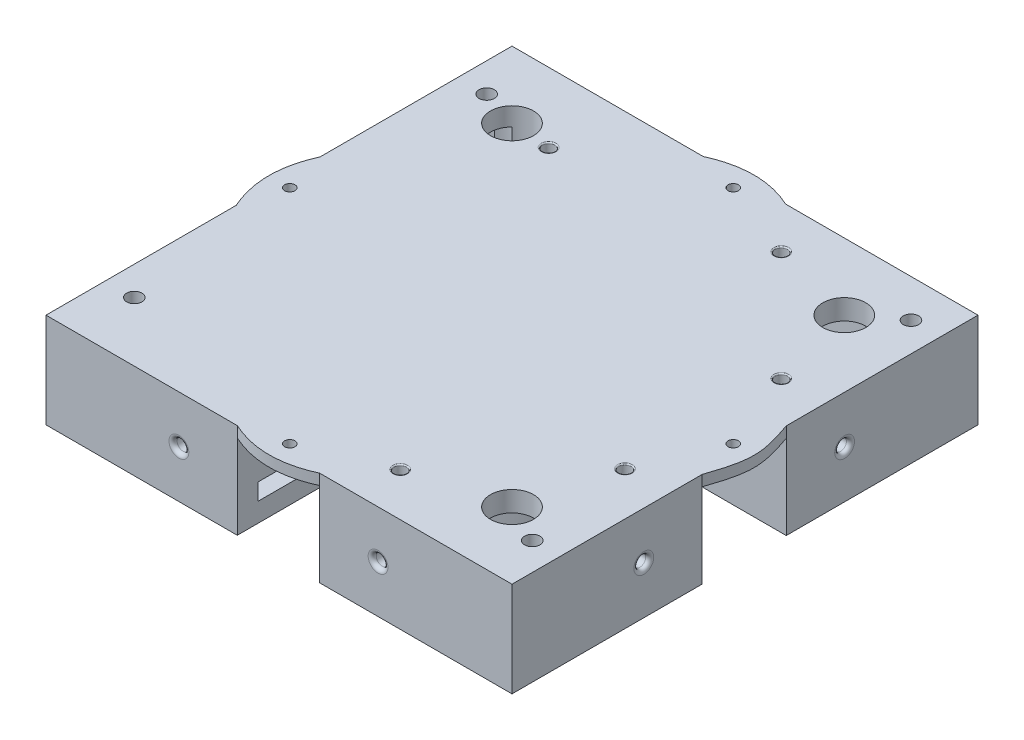
SolidWorks part; units mm, degrees
material "5052-H32"
ref_plane "Front Plane" through (0, 0, 0) normal (0, 0, 1) x (1, 0, 0)
ref_plane "Top Plane" through (0, 0, 0) normal (0, 1, 0) x (1, 0, 0)
ref_plane "Right Plane" through (0, 0, 0) normal (1, 0, 0) x (0, 0, -1)
sketch "Sketch1" plane through (6.2102, 0, 5.115) normal (0, 1, 0) x (1, 0, 0)
  line L1 (-55.0729, 54.0753) -> (42.5271, 54.0753)
  line L2 (-55.0729, 54.0753) -> (-55.0729, -43.5247)
  line L3 (-55.0729, -43.5247) -> (42.5271, -43.5247)
  line L4 (42.5271, 54.0753) -> (42.5271, -43.5247)
  dimension "D1" = 97.6
  dimension "D2" = 97.6
extrude "Boss-Extrude1" add sketch "Sketch1" along normal blind 19.9
sketch "Sketch2" plane through (6.2102, 19.9, 5.115) normal (0, 1, 0) x (1, 0, 0)
  line L0 (42.5271, -43.5247) -> (42.5271, 54.0753) construction
  line L1 (-55.0729, -43.5247) -> (42.5271, -43.5247) construction
  circle A0 centre (28.5271, -29.5247) radius 4.5
  dimension "D1" = 9
  dimension "D2" = 14
  dimension "D3" = 14
sketch "Sketch3" plane through (6.2102, 19.9, 5.115) normal (0, 1, 0) x (1, 0, 0)
  line L0 (42.5271, -43.5247) -> (42.5271, 54.0753) construction
  line L1 (42.5271, 54.0753) -> (-55.0729, 54.0753) construction
  line L2 (-55.0729, 54.0753) -> (-55.0729, -43.5247) construction
  circle A0 centre (28.5271, 40.0753) radius 4.5
  circle A1 centre (-41.0729, 40.0753) radius 4.5
  dimension "D1" = 9
  dimension "D2" = 14
  dimension "D3" = 14
  dimension "D4" = 9
  dimension "D5" = 14
  dimension "D6" = 14
sketch "Sketch5" plane through (6.2102, 19.9, 5.115) normal (0, 1, 0) x (1, 0, 0)
  line L1 (-55.0729, 54.0753) -> (-55.0729, -43.5247) construction
  line L3 (-55.0729, -43.5247) -> (42.5271, -43.5247) construction
  circle A0 centre (-6.2729, 5.2753) radius 50.775
  dimension "D1" = 48.8
  dimension "D2" = 48.8
extrude "Cut-Extrude3" cut sketch "Sketch2" against normal blind 19.9 contours A0
extrude "Cut-Extrude5" cut sketch "Sketch3" against normal blind 19.9
sketch "Sketch7" plane through (6.2102, 19.9, 5.115) normal (0, 1, 0) x (1, 0, 0)
  line L0 (42.5271, -43.5247) -> (42.5271, 54.0753) construction
  line L1 (42.5271, 54.0753) -> (-55.0729, 54.0753) construction
  line L2 (42.5271, -43.5247) -> (42.5271, 54.0753) construction
  line L3 (-55.0729, -43.5247) -> (42.5271, -43.5247) construction
  line L4 (42.5271, 54.0753) -> (-55.0729, 54.0753) construction
  line L5 (-55.0729, 54.0753) -> (-55.0729, -43.5247) construction
  line L6 (-55.0729, 54.0753) -> (-55.0729, -43.5247) construction
  line L7 (-55.0729, -43.5247) -> (42.5271, -43.5247) construction
  circle A0 centre (36.4271, 46.1353) radius 1.6
  circle A1 centre (36.7271, -33.4747) radius 1.6
  circle A2 centre (-49.0229, 42.7253) radius 1.6
  circle A3 centre (-49.0229, -31.0747) radius 1.6
  dimension "D1" = 6.1
  dimension "D2" = 7.94
  dimension "D3" = 5.8
  dimension "D4" = 10.05
  dimension "D5" = 11.35
  dimension "D6" = 6.05
  dimension "D7" = 6.05
  dimension "D8" = 12.45
extrude "Cut-Extrude6" cut sketch "Sketch7" against normal blind 19.9
sketch "Sketch9" plane through (6.2102, 19.9, 5.115) normal (0, 1, 0) x (1, 0, 0)
  line L0 (42.5271, -43.5247) -> (42.5271, 54.0753) construction
  line L1 (42.5271, 54.0753) -> (-55.0729, 54.0753) construction
  line L2 (42.5271, -43.5247) -> (42.5271, 54.0753) construction
  line L3 (-55.0729, -43.5247) -> (42.5271, -43.5247) construction
  line L4 (42.5271, 54.0753) -> (-55.0729, 54.0753) construction
  line L5 (-55.0729, 54.0753) -> (-55.0729, -43.5247) construction
  circle A0 centre (33.4271, 21.9753) radius 1.3
  circle A1 centre (33.4271, -10.7747) radius 1.3
  circle A2 centre (10.4271, 44.9753) radius 1.3
  circle A3 centre (10.0271, -34.4247) radius 1.3
  circle A4 centre (-32.8529, 39.5253) radius 1.3
  dimension "D1" = 9.1
  dimension "D2" = 32.1
  dimension "D3" = 9.1
  dimension "D5" = 9.1
  dimension "D7" = 32.5
  dimension "D9" = 14.55
  dimension "D4" = 32.75
  dimension "D6" = 32.1
  dimension "D8" = 9.1
  dimension "D10" = 22.22
extrude "Cut-Extrude12" cut sketch "Sketch9" against normal blind 19.9
fillet "Fillet2" radius 0.25 1 edges at (16.6373, 19.9, -38.5603)
fillet "Fillet3" radius 0.25 1 edges at (39.6373, 19.9, -15.5603)
fillet "Fillet5" radius 0.25 3 edges at (16.2373, 19.9, 40.8397) (39.6373, 19.9, 17.1897) (-26.6427, 19.9, -33.1103)
sketch "Sketch16" plane through (0, 19.9, 0) normal (0, 1, 0) x (1, 0, 0)
  line L0 (-48.8627, 8.8) -> (-48.8627, -8.8)
  line L1 (-48.8627, 48.9603) -> (-48.8627, -48.6397) construction
  line L2 (0, 35.791) -> (0, -31.7052) construction
  line L3 (-25.3041, 0.1603) -> (24.6208, 0.1603) construction
  line L4 (48.7373, -48.6397) -> (48.7373, 48.9603) construction
  line L5 (-8.8, 48.9603) -> (8.8, 48.8)
  line L6 (48.7373, 48.9603) -> (-48.8627, 48.9603) construction
  line L7 (-8.8, -48.6397) -> (8.8, -48.4794)
  line L8 (48.7373, 8.8) -> (48.7373, -8.8)
  circle A0 centre (-0.0627, 0.1603) radius 50.775 construction
  spline S0 degree 2 poles (-48.8627, -8.8) (-52.8139, 0.0154) (-48.8627, 8.8) knots 0 0 0 1 1 1
  spline S1 degree 3 poles (48.7373, 8.8) (49.7135, 5.9213) (51.7006, 0.0624) (49.7364, -5.8119) (48.7373, -8.8) knots 0 0 0 0 0.491329 1 1 1 1
  spline S2 degree 2 poles (-8.8, 48.9603) (0.029, 52.9893) (8.8, 48.8) knots 0 0 0 1 1 1
  spline S3 degree 2 poles (-8.8, -48.6397) (0.029, -52.6688) (8.8, -48.4794) knots 0 0 0 1 1 1
  point P4 (-50.8375, 0)
  point P14 (48.7373, 8.8)
  point P15 (48.7373, -8.8)
  point P17 (50.712, 0)
  point P22 (0, 50.9353)
  point P27 (0, -50.6147)
extrude "Boss-Extrude3" add sketch "Sketch16" against normal blind 2.25
sketch "Sketch17" plane through (0, 19.9, 0) normal (0, 1, 0) x (1, 0, 0)
  line L0 (0, 36.9512) -> (0, -38.1962) construction
  line L1 (-17.9287, 0) -> (21.0682, 0) construction
  circle A0 centre (46.44, 0) radius 1.085
  circle A1 centre (-46.44, 0) radius 1.085
  circle A2 centre (0, 46.44) radius 1.085
  circle A3 centre (0, -46.44) radius 1.085
extrude "Cut-Extrude13" cut sketch "Sketch17" against normal blind 19.9
sketch "Sketch18" plane through (0, 0, 0) normal (0, -1, 0) x (1, 0, 0)
  line L0 (48.7373, 48.6397) -> (48.7373, -48.9603) construction
  line L1 (-48.8627, -8.8) -> (48.7373, -8.8)
  line L2 (-48.8627, -8.8) -> (-48.8627, 8.8)
  line L3 (-48.8627, 8.8) -> (48.7373, 8.8)
  line L4 (48.7373, -8.8) -> (48.7373, 8.8)
  line L5 (48.7373, -8.8) -> (48.7373, 8.8) construction
  line L7 (-8.8, 48.6397) -> (8.4578, 48.6397)
  line L8 (-8.8, 48.6397) -> (-8.8, -48.9603)
  line L9 (-8.8, -48.9603) -> (8.4578, -48.9603)
  line L10 (8.4578, 48.6397) -> (8.4578, -48.9603)
  circle A0 centre (0, 0) radius 32.5
extrude "Cut-Extrude14" cut sketch "Sketch18" against normal blind 17.65 contours L1 L4 L3 L2
sketch "Sketch19" plane through (0, 0, 0) normal (0, -1, 0) x (1, 0, 0)
  line L1 (-8.8, 48.6397) -> (8.4578, 48.6397)
  line L2 (-8.8, 48.6397) -> (-8.8, -48.9603)
  line L3 (-8.8, -48.9603) -> (8.4578, -48.9603)
  line L4 (8.4578, 48.6397) -> (8.4578, -48.9603)
extrude "Cut-Extrude15" cut sketch "Sketch19" against normal blind 17.65
sketch "Sketch20" plane through (0, 0, 0) normal (0, -1, 0) x (1, 0, 0)
  circle A0 centre (0, 0) radius 32.5
extrude "Cut-Extrude16" cut sketch "Sketch20" against normal blind 17.65
sketch "Sketch21" plane through (0, 0, 0) normal (0, -1, 0) x (-1, 0, 0)
  line L0 (-14.6078, 44.6603) -> (-36.2373, 44.6603)
  line L1 (-42.5873, 37.4103) -> (-52.6816, 37.4103) construction
  line L2 (-38.5119, 37.4103) -> (-42.5873, 37.4103)
  line L3 (-44.4373, 14.95) -> (-44.4373, 35.5603)
  line L4 (-38.0873, 42.8103) -> (-38.0873, 37.9649)
  line L8 (-31.2859, 8.8) -> (-48.7373, 8.8) construction
  line L9 (-31.2859, 8.8) -> (-48.7373, 8.8) construction
  line L10 (-44.4373, 14.95) -> (-40.3393, 14.95) construction
  line L11 (-42.5859, 13.1) -> (-33.9942, 13.1062)
  line L13 (-12.7578, 34.1264) -> (-12.7578, 42.8103)
  arc A1 (-36.2373, 44.6603) -> (-38.0873, 42.8103) centre (-36.2373, 42.8103) ccw
  circle A2 centre (-34.7373, 34.9603) radius 4.5 construction
  arc A3 (-44.4373, 14.95) -> (-42.5859, 13.1) centre (-42.5873, 14.95) ccw
  arc A4 (-33.9942, 13.1062) -> (-12.7578, 34.1264) centre (0, 0) cw
  arc A5 (-14.6078, 44.6603) -> (-12.7578, 42.8103) centre (-14.6078, 42.8103) cw
  arc A6 (-38.0873, 37.9649) -> (-38.5119, 37.4103) centre (-34.7373, 34.9603) ccw
  arc A7 (-42.5873, 37.4103) -> (-44.4373, 35.5603) centre (-42.5873, 35.5603) ccw
  point P4 (-12.7578, 42.8103)
  point P9 (-38.0914, 42.8103)
  point P16 (-44.4373, 35.5603)
  point P24 (-42.5873, 13.1)
  dimension "D1" = 1.85
  dimension "D7" = 6.15
  dimension "D9" = 4.3
sketch "Sketch24" plane through (0, 0, 0) normal (0, -1, 0) x (-1, 0, 0)
  line L0 (-12.7636, -42.5054) -> (-12.7636, -34.5156)
  line L2 (-30.2373, -34.6397) -> (-39.2373, -34.6397) construction
  line L3 (-48.7373, -48.6397) -> (-48.7373, -8.8) construction
  line L4 (-44.4373, -14.95) -> (-44.4373, -34.5)
  line L5 (-42.5873, -36.35) -> (-38.8996, -36.35)
  line L6 (-37.9519, -37.7887) -> (-37.9519, -42.4897)
  line L8 (-36.1019, -44.3397) -> (-14.6078, -44.3397)
  line L10 (-34.3894, -13.1) -> (-42.5873, -13.1)
  arc A0 (-42.5873, -13.1) -> (-44.4373, -14.95) centre (-42.5873, -14.95) ccw
  arc A1 (-44.4373, -34.5) -> (-42.5873, -36.35) centre (-42.5873, -34.5) ccw
  circle A2 centre (-34.7373, -34.6397) radius 4.5 construction
  arc A3 (-38.8996, -36.35) -> (-37.9519, -37.7887) centre (-34.7373, -34.6397) ccw
  arc A4 (-37.9519, -42.4897) -> (-36.1019, -44.3397) centre (-36.1019, -42.4897) ccw
  arc A5 (-14.6078, -44.3397) -> (-12.7636, -42.5054) centre (-14.6136, -42.4897) ccw
  arc A6 (-12.7636, -34.5156) -> (-34.3894, -13.1) centre (0, 0) cw
  point P7 (-44.4373, -14.95)
  point P11 (-42.5873, -36.35)
  point P23 (-36.1019, -44.3397)
  point P27 (-12.7578, -42.4897)
  dimension "D2" = 6.15
extrude "Cut-Extrude19" cut sketch "Sketch24" against normal blind 13
sketch "Sketch25" plane through (0, 13, 0) normal (0, -1, 0) x (1, 0, 0)
  line L0 (42.5873, 18.6797) -> (34.1918, 18.6797)
  line L1 (44.4373, 14.95) -> (44.4373, 34.5) construction
  line L2 (44.4373, 20.5297) -> (44.4373, 34.5)
  line L3 (44.4373, 14.95) -> (44.4373, 34.5) construction
  line L4 (42.5873, 36.35) -> (38.8996, 36.35)
  line L5 (42.5873, 36.35) -> (38.8996, 36.35) construction
  line L6 (36.1019, 44.3397) -> (14.6078, 44.3397) construction
  line L7 (19.7073, 42.4897) -> (19.7073, 34.6397)
  line L8 (33.5229, 38.9727) -> (33.5229, 42.4897)
  line L9 (36.1019, 44.3397) -> (14.6078, 44.3397) construction
  line L10 (21.5573, 44.3397) -> (31.6729, 44.3397)
  arc A0 (42.5873, 18.6797) -> (44.4373, 20.5297) centre (42.5873, 20.5297) ccw
  arc A1 (44.4373, 34.5) -> (42.5873, 36.35) centre (42.5873, 34.5) ccw
  arc A2 (44.4373, 34.5) -> (42.5873, 36.35) centre (42.5873, 34.5) ccw construction
  arc A3 (19.7073, 42.4897) -> (21.5573, 44.3397) centre (21.5573, 42.4897) cw
  arc A4 (38.8996, 36.35) -> (33.5229, 38.9727) centre (34.7373, 34.6397) ccw
  arc A5 (33.5229, 42.4897) -> (31.6729, 44.3397) centre (31.6729, 42.4897) ccw
  arc A7 (34.3894, 13.1) -> (12.7636, 34.5156) centre (0, 0) ccw construction
  arc A8 (20.5983, 30.4951) -> (30.5272, 20.5506) centre (0, 0) cw
  spline S0 degree 2 poles (34.1918, 18.6797) (31.9769, 18.8503) (30.5272, 20.5506) knots 0 0 0 1 1 1
  spline S1 degree 2 poles (19.7073, 34.6397) (19.7281, 32.4756) (20.5983, 30.4951) knots 0 0 0 1 1 1
  point P2 (44.4373, 20.5297)
  point P21 (31.6729, 44.3397)
  point P28 (21.5573, 44.3397)
  point P34 (32.2408, 19.1964)
  point P39 (20.5983, 30.4951)
  point P41 (19.9449, 32.5008)
extrude "Cut-Extrude20" cut sketch "Sketch25" against normal blind 2.65
extrude "Cut-Extrude21" cut sketch "Sketch21" against normal blind 13
sketch "Sketch27" plane through (0, 0, 0) normal (0, -1, 0) x (1, 0, 0)
  line L0 (-35.6365, 44.3397) -> (-14.9738, 44.3397)
  line L1 (-13.1, 42.4899) -> (-13.1, 34.3894)
  line L2 (-34.3894, 13.1) -> (-42.7127, 13.1)
  line L3 (-48.8627, 8.8) -> (-48.8627, 48.6397) construction
  line L4 (-37.4865, 42.4897) -> (-37.4865, 38.6397)
  line L5 (-50.8377, -0.1603) -> (50.7123, -0.1603) construction
  line L6 (-0.0627, 50.6147) -> (-0.0627, -50.9353) construction
  line L8 (-44.5627, 35.5497) -> (-44.5627, 14.95)
  line L9 (-37.4865, 38.6397) -> (-42.7127, 38.6397)
  arc A0 (-14.9738, 44.3397) -> (-13.1, 42.4899) centre (-14.95, 42.4899) cw
  circle A1 centre (-0.0627, -0.1603) radius 50.775 construction
  arc A2 (-13.1, 34.3894) -> (-34.3894, 13.1) centre (0, 0) ccw
  arc A3 (-35.6365, 44.3397) -> (-37.4865, 42.4897) centre (-35.6365, 42.4897) ccw
  arc A4 (-42.7127, 13.1) -> (-44.5627, 14.95) centre (-42.7127, 14.95) cw
  circle A5 centre (-42.8127, 36.1897) radius 1.6 construction
  arc A6 (-42.7127, 38.6397) -> (-44.4062, 36.0449) centre (-42.7127, 36.7897) ccw
  arc A7 (-44.4062, 36.0449) -> (-44.5627, 35.5497) centre (-43.2956, 35.4214) ccw
  parabola Q0 (-8.8, 48.6397) -> (8.4578, 48.6397) focus (-0.0906, 41.1914) apex (-0.0241, 50.6145) construction
  point P2 (-37.4627, 42.4897)
  point P21 (-13.1, 42.4897)
  point P24 (-42.7127, 13.1)
  point P31 (-44.5627, 14.95)
  dimension "D2" = 6.15
extrude "Cut-Extrude22" cut sketch "Sketch27" against normal blind 15.65
sketch "Sketch28" plane through (0, 0, 0) normal (0, -1, 0) x (1, 0, 0)
  line L0 (-42.7127, -13.1) -> (-34.3894, -13.1)
  line L1 (-44.4037, -37.4409) -> (-44.4037, -14.95)
  line L2 (-38.0447, -38.1423) -> (-38.0447, -42.8103)
  line L3 (-36.1947, -44.6603) -> (-14.95, -44.6603)
  line L4 (-8.8, -31.2859) -> (-8.8, -48.9603) construction
  line L5 (-13.1, -34.3894) -> (-13.1, -42.8103)
  line L10 (-8.8, -48.9603) -> (-48.8627, -48.9603) construction
  arc A0 (-42.7127, -13.1) -> (-44.4037, -14.95) centre (-42.5463, -14.95) ccw
  circle A1 centre (-42.8127, -37.6103) radius 1.6 construction
  circle A2 centre (-34.8627, -34.9603) radius 4.5 construction
  circle A3 centre (-42.8127, -37.6103) radius 1.6
  arc A4 (-38.0447, -42.8103) -> (-36.1947, -44.6603) centre (-36.1947, -42.8103) ccw
  arc A5 (-14.95, -44.6603) -> (-13.1, -42.8103) centre (-14.95, -42.8103) ccw
  arc A6 (-13.1, -34.3894) -> (-34.3894, -13.1) centre (0, 0) cw
  spline S0 degree 2 poles (-38.0447, -38.1423) (-39.7881, -41.8175) (-42.8127, -39.2103) knots 0 0 0 1 1 1
  point P4 (-44.5627, -14.95)
  point P14 (-36.1947, -44.6603)
  point P24 (-40.1783, -40.2611)
  point P27 (-13.1, -42.8103)
  circle M12 centre (-34.8627, -34.9603) radius 4.5
  circle M13 centre (-42.8127, -37.6103) radius 1.6
  circle M14 centre (-26.6427, -34.4103) radius 1.3
  dimension "D1" = 10.818
  dimension "D2" = 6.15
extrude "Cut-Extrude23" cut sketch "Sketch28" against normal blind 9.2 contours S0 L2 A4 L3 A5 L5 A6 L0 A0 L1 M12 M13 M14 | A3 M13 | M12 region at (-34.8627, 0, -34.9603) region at (-30.9777, 0, -31.133) region at (-42.8127, 0, -37.6103)
sketch "Sketch30" plane through (0, 9.2, 0) normal (0, -1, 0) x (1, 0, 0)
  line L0 (-34.3894, -13.1) -> (-42.7127, -13.1)
  line L1 (-44.4037, -14.95) -> (-44.4037, -37.4409)
  line L2 (-39.3627, -34.9603) -> (-30.3627, -34.9603) construction
  line L3 (-27.6026, -27.7002) -> (-31.6807, -31.7783)
  arc A1 (-34.3894, -13.1) -> (-13.1, -34.3894) centre (0, 0) ccw construction
  arc A2 (-26.9237, -25.087) -> (-34.3894, -13.1) centre (0, 0) cw
  arc A3 (-42.7127, -13.1) -> (-44.4037, -14.95) centre (-42.5463, -14.95) ccw
  circle A5 centre (-34.8627, -34.9603) radius 4.5 construction
  arc A7 (-42.8127, -39.2103) -> (-44.4037, -37.4409) centre (-42.8127, -37.6103) ccw construction
  arc A8 (-38.0447, -38.1423) -> (-31.6807, -31.7783) centre (-34.8627, -34.9603) cw
  arc A9 (-42.8127, -39.2103) -> (-44.4037, -37.4409) centre (-42.8127, -37.6103) ccw
  parabola Q2 (-38.0447, -38.1423) -> (-42.8127, -39.2103) focus (-40.3293, -39.3425) apex (-40.1433, -40.2543) construction
  parabola Q3 (-38.0447, -38.1423) -> (-42.8127, -39.2103) focus (-40.3293, -39.3425) apex (-40.1433, -40.2543)
  spline S0 degree 2 poles (-27.6026, -27.7002) (-26.4881, -26.626) (-26.9237, -25.087) knots 0 0 0 1 1 1
  point P4 (-44.4037, -14.95)
  point P9 (-26.9237, -26.67)
  point P10 (-26.9237, -25.087)
  point P24 (-40.199, -40.2684)
  point P27 (-38.0447, -38.1423)
extrude "Cut-Extrude24" cut sketch "Sketch30" against normal blind 6.85 contours L3 S0 A2 L0 A3 L1 A9 Q3 A8 region at (-37.6678, 9.2, -24.4447)
sketch "Sketch31" plane through (0, 13, 0) normal (0, -1, 0) x (1, 0, 0)
  line L0 (38.5119, -37.4103) -> (42.5873, -37.4103)
  line L1 (38.5119, -37.4103) -> (42.5873, -37.4103) construction
  line L2 (31.4637, -20.613) -> (42.5873, -20.613)
  line L3 (44.4373, -35.5603) -> (44.4373, -22.463)
  line L4 (22.3673, -44.6603) -> (32.8873, -44.6603)
  line L6 (34.7373, -39.4603) -> (34.7373, -42.8103)
  line L8 (20.5173, -42.8103) -> (20.5173, -31.9104)
  arc A0 (38.5119, -37.4103) -> (38.0873, -37.9649) centre (34.7373, -34.9603) ccw construction
  arc A1 (34.7373, -39.4603) -> (38.5119, -37.4103) centre (34.7373, -34.9603) cw
  arc A2 (42.5873, -37.4103) -> (44.4373, -35.5603) centre (42.5873, -35.5603) ccw
  arc A3 (42.5873, -37.4103) -> (44.4373, -35.5603) centre (42.5873, -35.5603) ccw construction
  arc A4 (34.7373, -42.8103) -> (32.8873, -44.6603) centre (32.8873, -42.8103) cw
  arc A5 (22.3673, -44.6603) -> (20.5173, -42.8103) centre (22.3673, -42.8103) cw
  arc A6 (44.4373, -22.463) -> (42.5873, -20.613) centre (42.5873, -22.463) ccw
  arc A7 (12.7578, -34.1264) -> (33.9942, -13.1062) centre (0, 0) ccw construction
  arc A8 (21.7165, -29.2536) -> (29.4236, -21.4855) centre (0, 0) ccw
  spline S0 degree 2 poles (31.4637, -20.613) (30.2943, -20.696) (29.4236, -21.4855) knots 0 0 0 1 1 1
  spline S1 degree 2 poles (20.5173, -31.9104) (20.595, -30.3481) (21.7165, -29.2536) knots 0 0 0 1 1 1
  point P0 (44.4373, -35.5603)
  point P13 (22.3673, -44.6603)
  point P19 (44.4373, -22.463)
  point P20 (30.3942, -20.862)
  point P22 (29.4236, -21.4855)
  point P26 (21.7165, -29.2536)
  point P34 (32.8873, -44.6603)
  point P37 (20.8481, -30.4826)
extrude "Cut-Extrude26" cut sketch "Sketch31" against normal blind 2.65
sketch "Sketch32" plane through (0, 0, 48.6397) normal (0, 0, 1) x (1, 0, 0)
  circle A0 centre (-21.025, 9.95) radius 1.225
  circle A1 centre (20.6828, 9.95) radius 1.225
extrude "Cut-Extrude27" cut sketch "Sketch32" against normal blind 4.4
fillet "Fillet6" radius 0.85 1 edges at (-19.8, 9.95, 48.6397)
fillet "Fillet7" radius 0.85 1 edges at (19.4578, 9.95, 48.6397)
sketch "Sketch33" plane through (48.7373, 0, 0) normal (1, 0, 0) x (0, 0, -1)
  line L0 (50.9353, 19.9) -> (-50.6147, 19.9) construction
  line L1 (-8.8, 17.65) -> (-8.8, 0) construction
  line L3 (-8.8, 17.65) -> (8.8, 17.65) construction
  line L4 (0, 17.65) -> (0, -3.9996) construction
  line L5 (8.8, 17.65) -> (8.8, 0) construction
  line L6 (8.8, 0) -> (48.9603, 0) construction
  line L7 (8.8, 19.9) -> (48.9603, 19.9) construction
  circle A0 centre (-21.025, 9.95) radius 1.225
  circle A1 centre (21.025, 9.95) radius 1.225
  dimension "D1" = 9.95
  dimension "D2" = 12.225
  dimension "D5" = 2.45
  dimension "D6" = 9.95
  dimension "D7" = 9.95
  dimension "D8" = 21.025
  dimension "D9" = 21.025
  dimension "D3" = 8.8
  dimension "D4" = 8.8
extrude "Cut-Extrude28" cut sketch "Sketch33" against normal blind 4.4
fillet "Fillet8" radius 0.85 1 edges at (48.7373, 9.95, 19.8)
fillet "Fillet9" radius 0.85 1 edges at (48.7373, 9.95, -19.8)
sketch "Sketch34" plane through (0, 0, -48.9603) normal (0, 0, -1) x (-1, 0, 0)
  line L0 (50.8377, 19.9) -> (-50.7123, 19.9) construction
  line L2 (-8.4578, 17.65) -> (-8.4578, 0) construction
  line L3 (-8.4578, 17.65) -> (8.8, 17.65) construction
  line L4 (0.1711, 17.65) -> (0.1711, -9.8959) construction
  line L5 (8.8, 17.65) -> (8.8, 0) construction
  circle A0 centre (-20.6828, 9.95) radius 1.225
  circle A1 centre (21.025, 9.95) radius 1.225
  dimension "D1" = 9.95
  dimension "D2" = 12.225
  dimension "D3" = 12.225
extrude "Cut-Extrude29" cut sketch "Sketch34" against normal blind 6.5
fillet "Fillet10" radius 0.85 1 edges at (19.4578, 9.95, -48.9603)
fillet "Fillet11" radius 0.85 1 edges at (-19.8, 9.95, -48.9603)
sketch "Sketch35" plane through (-48.8627, 0, 0) normal (-1, 0, 0) x (0, 0, 1)
  line L0 (50.6147, 19.9) -> (-50.9353, 19.9) construction
  circle A0 centre (-21.025, 9.95) radius 1.225
  circle A1 centre (21.025, 9.95) radius 1.225
  dimension "D1" = 9.95
extrude "Cut-Extrude30" cut sketch "Sketch35" against normal blind 4.4
fillet "Fillet12" radius 0.85 1 edges at (-48.8627, 9.95, -19.8)
fillet "Fillet13" radius 0.85 1 edges at (-48.8627, 9.95, 19.8)
sketch "Sketch38" plane through (8.4578, 0, 0) normal (-1, 0, 0) x (0, 0, 1)
  line L0 (-41.9603, 4) -> (-29.4603, 4)
  line L1 (-48.9603, 0) -> (-31.3802, 0) construction
  line L2 (-48.9603, 17.65) -> (-48.9603, 0) construction
  line L3 (-41.9603, 7.5) -> (-29.4603, 7.5)
  line L4 (-41.9603, 4) -> (-41.9603, 7.5)
  line L5 (-29.4603, 4) -> (-29.4603, 7.5)
  dimension "D1" = 4
  dimension "D2" = 7
  dimension "D3" = 19.5
  dimension "D4" = 3.5
extrude "Cut-Extrude31" cut sketch "Sketch38" against normal blind 6.85
sketch "Sketch39" plane through (8.4578, 0, 0) normal (-1, 0, 0) x (0, 0, 1)
  line L0 (-37.6507, 7.5) -> (-37.6507, 4) construction
  line L1 (-44.6603, 4) -> (-37.6507, 4)
  line L2 (-41.9603, 4) -> (-31.3802, 4) construction
  line L5 (-37.6507, 4) -> (-37.6507, 7.5)
  line L6 (-44.6603, 7.5) -> (-44.6603, 4)
  line L8 (-31.3802, 7.5) -> (-41.9603, 7.5) construction
  line L9 (-37.6507, 7.5) -> (-44.6603, 7.5)
revolve "Cut-Revolve1" cut sketch "Sketch39" angle 90 about L0
sketch "Sketch40" plane through (0, 0, 8.8) normal (0, 0, -1) x (-1, 0, 0)
  line L0 (-41.7373, 4) -> (-29.2373, 4)
  line L1 (-31.2859, 0) -> (-48.7373, 0) construction
  line L4 (-41.7373, 7.5) -> (-29.2373, 7.5)
  line L6 (-29.2373, 4) -> (-29.2373, 7.5)
  line L7 (-41.7373, 7.5) -> (-41.7373, 4)
  dimension "D1" = 4
extrude "Cut-Extrude33" cut sketch "Sketch40" against normal blind 6.85
sketch "Sketch41" plane through (0, 0, 8.8) normal (0, 0, -1) x (-1, 0, 0)
  line L0 (-41.7373, 4) -> (-44.4373, 4)
  line L1 (-48.7373, 17.65) -> (-48.7373, 0) construction
  line L2 (-41.7373, 7.5) -> (-44.4373, 7.5)
  line L3 (-44.4373, 7.5) -> (-44.4373, 4)
  line L4 (-41.7373, 4) -> (-41.7373, 7.5)
  line L5 (-34.7373, 4) -> (-34.7373, 7.5) construction
  line L8 (-41.7373, 4) -> (-31.2859, 4) construction
  line L9 (-31.2859, 7.5) -> (-41.7373, 7.5) construction
  dimension "D1" = 4.3
  dimension "D2" = 7
revolve "Cut-Revolve2" cut sketch "Sketch41" angle 90 about L5 reverse direction yes
sketch "Sketch42" plane through (0, 0, -8.8) normal (0, 0, 1) x (1, 0, 0)
  line L0 (-41.8627, 4) -> (-29.3627, 4)
  line L1 (-48.8627, 17.65) -> (-48.8627, 0) construction
  line L2 (-48.8627, 0) -> (-31.2859, 0) construction
  line L3 (-41.8627, 4) -> (-41.8627, 7.5)
  line L4 (-41.8627, 7.5) -> (-29.3627, 7.5)
  line L5 (-29.3627, 7.5) -> (-29.3627, 4)
  dimension "D1" = 7
  dimension "D2" = 3.5
  dimension "D3" = 4
extrude "Cut-Extrude34" cut sketch "Sketch42" against normal blind 6.85
sketch "Sketch43" plane through (0, 0, -8.8) normal (0, 0, 1) x (1, 0, 0)
  line L0 (-41.8627, 4) -> (-44.5627, 4)
  line L1 (-48.8627, 17.65) -> (-48.8627, 0) construction
  line L2 (-41.8627, 7.5) -> (-44.5627, 7.5)
  line L3 (-44.5627, 7.5) -> (-44.5627, 4)
  line L4 (-41.8627, 7.5) -> (-41.8627, 4) construction
  line L5 (-34.8627, 4) -> (-34.8627, 7.5) construction
  line L6 (-41.8627, 4) -> (-31.2859, 4) construction
  line L7 (-31.2859, 7.5) -> (-41.8627, 7.5) construction
  line L8 (-41.8627, 7.5) -> (-41.8627, 4)
  point P8 (-41.8627, 5.75)
  dimension "D1" = 4.3
  dimension "D2" = 2.7
  dimension "D3" = 7
revolve "Cut-Revolve3" cut sketch "Sketch43" angle 90 about L5 reverse direction yes
sketch "Sketch45" plane through (0, 0, -29.4603) normal (0, 0, -1) x (-1, 0, 0)
  line L0 (-13.7237, 7.5) -> (-13.7237, 4)
  line L1 (-13.7237, 7.5) -> (-13.7237, 4) construction
  line L2 (-13.7237, 4) -> (-15.3078, 4)
  line L3 (-15.3078, 4) -> (-15.3078, 7.5)
  line L4 (-15.3078, 7.5) -> (-13.7237, 7.5)
extrude "Cut-Extrude35" cut sketch "Sketch45" against normal blind 1.5
sketch "Sketch46" plane through (29.2373, 0, 0) normal (1, 0, 0) x (0, 0, -1)
  line L0 (-14.1927, 7.5) -> (-14.1927, 4)
  line L1 (-14.1927, 7.5) -> (-14.1927, 4) construction
  line L2 (-14.1927, 4) -> (-15.65, 4)
  line L3 (-15.65, 4) -> (-15.65, 7.5)
  line L4 (-15.65, 7.5) -> (-14.1927, 7.5)
extrude "Cut-Extrude37" cut sketch "Sketch46" against normal blind 1.5
sketch "Sketch47" plane through (-29.3627, 0, 0) normal (-1, 0, 0) x (0, 0, 1)
  line L0 (-13.9313, 7.5) -> (-13.9313, 4)
  line L1 (-13.9313, 7.5) -> (-13.9313, 4) construction
  line L2 (-13.9313, 4) -> (-15.65, 4)
  line L3 (-15.65, 4) -> (-15.65, 7.5)
  line L4 (-15.65, 7.5) -> (-13.9313, 7.5)
extrude "Cut-Extrude38" cut sketch "Sketch47" against normal blind 1.5
sketch "Sketch48" plane through (-8.8, 0, 0) normal (1, 0, 0) x (0, 0, -1)
  line L0 (-41.6397, 4) -> (-29.1397, 4)
  line L1 (-48.6397, 17.65) -> (-48.6397, 0) construction
  line L2 (-48.6397, 0) -> (-31.2859, 0) construction
  line L3 (-41.6397, 4) -> (-41.6397, 7.5)
  line L4 (-41.6397, 7.5) -> (-29.1397, 7.5)
  line L5 (-29.1397, 7.5) -> (-29.1397, 4)
  dimension "D1" = 7
  dimension "D2" = 19.5
  dimension "D3" = 4
  dimension "D4" = 3.5
extrude "Cut-Extrude39" cut sketch "Sketch48" against normal blind 6.85
sketch "Sketch49" plane through (0, 0, 29.1397) normal (0, 0, 1) x (1, 0, 0)
  line L0 (-14.3919, 7.5) -> (-14.3919, 4)
  line L1 (-14.3919, 4) -> (-15.65, 4)
  line L2 (-15.65, 4) -> (-15.65, 7.5)
  line L3 (-15.65, 7.5) -> (-14.3919, 7.5)
extrude "Cut-Extrude40" cut sketch "Sketch49" against normal blind 1.5
sketch "Sketch50" plane through (-8.8, 0, 0) normal (1, 0, 0) x (0, 0, -1)
  line L0 (-41.6397, 4) -> (-44.3397, 4)
  line L2 (-41.6397, 7.5) -> (-44.3397, 7.5)
  line L3 (-44.3397, 7.5) -> (-44.3397, 4)
  line L6 (-34.6397, 4) -> (-34.6397, 7.5) construction
  line L7 (-41.6397, 4) -> (-31.2859, 4) construction
  line L8 (-31.2859, 7.5) -> (-41.6397, 7.5) construction
  line L9 (-41.6397, 7.5) -> (-41.6397, 4) construction
  line L10 (-41.6397, 7.5) -> (-41.6397, 4)
  dimension "D1" = 7
revolve "Cut-Revolve5" cut sketch "Sketch50" angle 90 about L6 reverse direction yes
sketch "Sketch51" plane through (0, 0, -8.8) normal (0, 0, 1) x (1, 0, 0)
  line L0 (-44.5627, 4) -> (-31.2859, 4) construction
  line L1 (-34.5946, 4) -> (-34.5946, 0)
  line L2 (-48.8627, 0) -> (-31.2859, 0) construction
  line L3 (-34.5946, 0) -> (-39.866, 0)
  line L4 (-39.866, 0) -> (-39.866, 4)
  arc A0 (-39.866, 4) -> (-34.5946, 4) centre (-37.2303, 6.7897) cw
  point P0 (-37.2303, 6.7897)
extrude "Cut-Extrude41" cut sketch "Sketch51" against normal blind 7
sketch "Sketch52" plane through (0, 17.65, 0) normal (0, -1, 0) x (-1, 0, 0)
  line L0 (0, 46.44) -> (0.0241, 50.9351)
  parabola Q2 (-8.4578, 48.9603) -> (8.8, 48.9603) focus (0.0906, 41.512) apex (0.0241, 50.9351) construction
